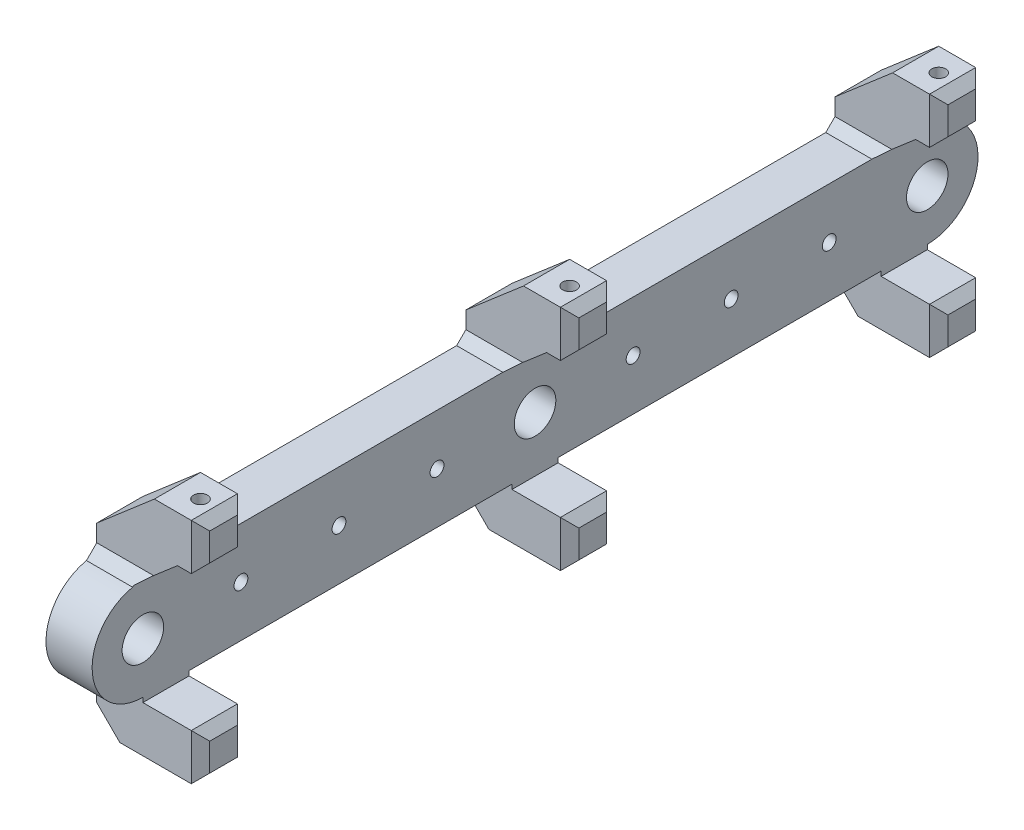
SolidWorks part; units mm, degrees
ref_plane "Front Plane" through (0, 0, 0) normal (0, 0, 1) x (1, 0, 0)
ref_plane "Top Plane" through (0, 0, 0) normal (0, 1, 0) x (1, 0, 0)
ref_plane "Right Plane" through (0, 0, 0) normal (1, 0, 0) x (0, 0, -1)
sketch "Sketch1" plane through (0, 0, 0) normal (1, 0, 0) x (0, 0, -1)
  line L0 (0, 0) -> (170, 0) construction
  line L1 (0, 11) -> (170, 11)
  line L2 (0, -11) -> (170, -11)
  circle A0 centre (0, 0) radius 4.5
  arc A1 (0, 11) -> (0, -11) centre (0, 0) ccw
  arc A2 (170, -11) -> (170, 11) centre (170, 0) ccw
  circle A3 centre (0, 0) radius 35 construction
  circle A4 centre (85, 0) radius 35 construction
  circle A5 centre (170, 0) radius 35 construction
  circle A6 centre (85, 0) radius 4.5
  circle A7 centre (170, 0) radius 4.5
  point P3 (85, 0)
  dimension "D1" = 85
  dimension "D3" = 70
  dimension "D4" = 9
  dimension "D2" = 85
extrude "Boss-Extrude1" add sketch "Sketch1" along normal blind 10 contours A0 | A6 | A7 | L1 A2 L2 A1 region at (0, 0, 0) region at (0, 0, -85) region at (0, 0, -170)
sketch "Sketch3" plane through (0, 0, 0) normal (-1, 0, 0) x (0, 0, 1)
  line L0 (-63.75, 0) -> (-42.5, 0) construction
  line L1 (-42.5, 0) -> (-21.25, 0) construction
  line L2 (-85, 0) -> (-63.75, 0) construction
  line L3 (-21.25, 0) -> (0, 0) construction
  line L4 (-170, 0) -> (-148.75, 0) construction
  line L5 (-148.75, 0) -> (-127.5, 0) construction
  line L6 (-127.5, 0) -> (-106.25, 0) construction
  line L7 (-106.25, 0) -> (-85, 0) construction
  circle A2 centre (-42.5, 0) radius 1.5
  circle A3 centre (-63.75, 0) radius 1.5
  circle A4 centre (-21.25, 0) radius 1.5
  circle A5 centre (-148.75, 0) radius 1.5
  circle A6 centre (-127.5, 0) radius 1.5
  circle A7 centre (-106.25, 0) radius 1.5
  dimension "D1" = 3
extrude "Cut-Extrude1" cut sketch "Sketch3" against normal through all
sketch "Sketch6" plane through (10, 0, 0) normal (1, 0, 0) x (0, 0, -1)
  circle A0 centre (106.25, 0) radius 10.4
  circle A1 centre (127.5, 0) radius 10.4
  circle A2 centre (148.75, 0) radius 10.4
  circle A3 centre (85, 0) radius 10.5
  circle A4 centre (170, 0) radius 10.5
  circle A5 centre (63.75, 0) radius 10.5
  circle A6 centre (42.5, 0) radius 10.5
  circle A7 centre (21.25, -0.085) radius 10.5
sketch "Sketch7" plane through (0, 0, 0) normal (0, 0, 1) x (1, 0, 0)
  line L0 (10, -10.5) -> (10, 10.5) construction
  line L1 (0, 11) -> (0, 16.6971)
  line L3 (0, 11) -> (10, 11)
  line L4 (22.4897, 27.4454) -> (12.4897, 27.4454)
  line L5 (5.2275, 15.015) -> (5.4467, 43.2136) construction
  line L6 (22.4897, 17.4454) -> (17.4897, 17.4454)
  line L7 (12.4897, 27.4454) -> (0, 16.6971)
  line L8 (17.4897, 17.4454) -> (10, 11)
  line L9 (22.4897, 17.4454) -> (22.4897, 27.4454)
  dimension "D1" = 10
  dimension "D2" = 10
extrude "Boss-Extrude2" add sketch "Sketch7" against normal blind 10 separate body
ref_point "Point1"
ref_point "Point2"
ref_axis "Axis1" through (10, 0, -85) along (-1, 0, 0)
ref_plane "Plane1" through (0, 0, -85) normal (0, 0, -1) x (-1, 0, 0)
pattern_linear "LPattern1" count 3 spacing 80 along (0, 0, -1) of "Boss-Extrude2"
combine bodies "Combine1" operation type add bodies to combine 109 103 108 106
chamfer "Chamfer2" distance 2 angle 45 6 edges at (5, 11, -10) (5, 11, 0) (5, 11, -80) (5, 11, -90) (5, 11, -170) (5, 11, -160)
sketch "Sketch8" plane through (0, -11, 0) normal (0, -1, 0) x (-1, 0, 0)
  line L0 (-10, 0) -> (0, 0)
  line L1 (0, 0) -> (0, 10)
  line L2 (0, 10) -> (-10, 10)
  line L3 (-10, 10) -> (-10, 0)
extrude "Boss-Extrude3" add sketch "Sketch8" along normal blind 1
sketch "Sketch10" plane through (10, 0, 0) normal (1, 0, 0) x (0, 0, -1)
  line L0 (10, -12) -> (10, -22)
  line L1 (10, -22) -> (0, -22)
  line L2 (0, -22) -> (0, -12)
  line L3 (0, -12) -> (10, -12)
extrude "Boss-Extrude5" add sketch "Sketch10" along normal up to surface (12.4897 mm away) and the other way blind 10 up to face at (22.4897, 22.4454, -5)
chamfer "Chamfer3" distance 5 angle 45 1 edges at (0, -22, -5)
pattern_linear "LPattern3" count 3 spacing 80 along (0, 0, -1) of "Boss-Extrude5", "Boss-Extrude3", "Chamfer3"
sketch "Sketch12" plane through (0, 27.4454, 0) normal (0, 1, 0) x (1, 0, 0)
  line L0 (17.4897, 10) -> (17.4897, 0) construction
  line L1 (22.4897, 10) -> (12.4897, 10) construction
  line L2 (17.4897, 90) -> (17.4897, 80) construction
  line L3 (22.4897, 90) -> (12.4897, 90) construction
  line L4 (22.4897, 80) -> (12.4897, 80) construction
  line L5 (17.4897, 170) -> (17.4897, 160) construction
  line L6 (22.4897, 170) -> (12.4897, 170) construction
  line L7 (22.4897, 160) -> (12.4897, 160) construction
  circle A0 centre (17.4897, 5) radius 1.5
  circle A1 centre (17.4897, 165) radius 1.5
  circle A2 centre (17.4897, 85) radius 1.5
extrude "Cut-Extrude2" cut sketch "Sketch12" against normal blind 7
sketch "Sketch13" plane through (0, -22, 0) normal (0, -1, 0) x (-1, 0, 0)
  line L0 (-17.4897, 170) -> (-17.4897, 160) construction
  line L1 (-17.4897, 90) -> (-17.4897, 80) construction
  line L2 (-17.4897, 10) -> (-17.4897, 0) construction
  circle A0 centre (-17.4897, 165) radius 1.5
  circle A1 centre (-17.4897, 85) radius 1.5
  circle A2 centre (-17.4897, 5) radius 1.5
extrude "Cut-Extrude3" cut sketch "Sketch13" against normal blind 7
chamfer "Chamfer4" distance 2 angle 45 24 edges at (22.4897, 27.4454, -165) (22.4897, 22.4454, -170) (22.4897, 17.4454, -165) (22.4897, 22.4454, -160) (22.4897, -22, -5) (22.4897, -17, 0) (22.4897, -12, -5) (22.4897, -17, -10) (22.4897, -22, -85) (22.4897, -17, -80) (22.4897, -12, -85) (22.4897, -17, -90) (22.4897, -22, -165) (22.4897, -17, -160) (22.4897, -12, -165) (22.4897, -17, -170) (22.4897, 17.4454, -85) (22.4897, 22.4454, -80) (22.4897, 27.4454, -85) (22.4897, 22.4454, -90) (22.4897, 22.4454, -10) (22.4897, 17.4454, -5) (22.4897, 22.4454, 0) (22.4897, 27.4454, -5)
sketch "Sketch14" plane through (0, 0, 0) normal (-1, 0, 0) x (0, 0, 1)
  line L1 (-184.9305, -31.2602) -> (14.9305, -31.2602)
  line L2 (-184.9305, -31.2602) -> (-184.9305, 31.2602)
  line L3 (-184.9305, 31.2602) -> (14.9305, 31.2602)
  line L4 (14.9305, -31.2602) -> (14.9305, 31.2602)
  line L5 (-184.9305, -31.2602) -> (14.9305, 31.2602) construction
  line L6 (-184.9305, 31.2602) -> (14.9305, -31.2602) construction
  point P0 (-85, 0)
